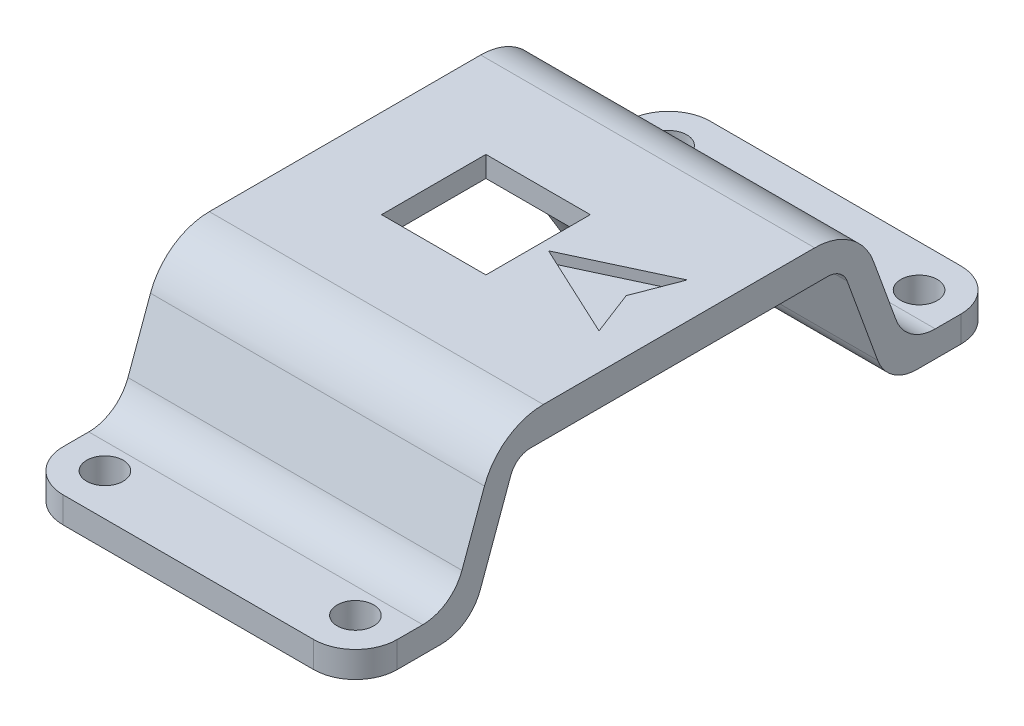
SolidWorks part; units mm, degrees
ref_plane "Спереди" through (0, 0, 0) normal (0, 0, 1) x (1, 0, 0)
ref_plane "Сверху" through (0, 0, 0) normal (0, 1, 0) x (1, 0, 0)
ref_plane "Справа" through (0, 0, 0) normal (1, 0, 0) x (0, 0, -1)
sketch "Эскиз1" plane through (0, 0, 0) normal (1, 0, 0) x (0, 0, -1)
  line L0 (0, 0) -> (0, 19.8413) construction
  line L1 (-31, 0) -> (-20, 0)
  line L2 (-20, 0) -> (-15.6324, 12)
  line L3 (-15.6324, 12) -> (15.6324, 12)
  line L4 (-31, 0) -> (-31, 2.5)
  line L5 (-31, 2.5) -> (-21.7505, 2.5)
  line L6 (-21.7505, 2.5) -> (-17.2009, 15)
  line L7 (-17.2009, 15) -> (17.2009, 15)
  line L8 (21.7505, 2.5) -> (17.2009, 15)
  line L9 (31, 2.5) -> (21.7505, 2.5)
  line L10 (31, 0) -> (31, 2.5)
  line L11 (20, 0) -> (15.6324, 12)
  line L12 (31, 0) -> (20, 0)
  point P14 (0, 15)
  point P18 (0, 12)
  dimension "D1" = 31
  dimension "D2" = 2.5
  dimension "D3" = 3
  dimension "D4" = 2.5
  dimension "D5" = 12
  dimension "D6" = 20
  dimension "D7" = 110
extrude "Бобышка-Вытянуть1" add sketch "Эскиз1" along normal blind 32
sketch "Эскиз2" plane through (0, 0, 0) normal (0, -1, 0) x (1, 0, 0)
  line L0 (0, 0) -> (39.3934, 0) construction
  line L1 (16, 31) -> (16, -31) construction
  line L2 (32, 31) -> (0, 31) construction
  line L3 (32, -31) -> (0, -31) construction
  circle A0 centre (4, 27) radius 1.75
  dimension "D1" = 3.5
  dimension "D2" = 27
  dimension "D3" = 12
extrude "Вырез-Вытянуть1" cut sketch "Эскиз2" against normal through all
pattern_linear "Линейный массив1" count 2 spacing 24 along (1, 0, 0) count 2 spacing 54 along (0, 0, -1) of "Вырез-Вытянуть1"
fillet "Скругление1" radius 4 4 edges at (32, 1.25, -31) (0, 1.25, -31) (0, 1.25, 31) (32, 1.25, 31)
sketch "Эскиз3" plane through (0, 12, 0) normal (0, -1, 0) x (1, 0, 0)
  line L0 (0, 0) -> (32, 0) construction
  line L1 (0, 15.6324) -> (0, -15.6324) construction
  line L2 (32, 15.6324) -> (32, -15.6324) construction
  line L3 (16, 15.6324) -> (16, -15.6324) construction
  line L4 (32, 15.6324) -> (0, 15.6324) construction
  line L5 (32, -15.6324) -> (0, -15.6324) construction
  line L6 (4, 15.6324) -> (4, -15.6324) construction
  line L7 (28, 15.6324) -> (28, -15.6324) construction
  circle A0 centre (26, 10.5) radius 1
  circle A1 centre (26, 10.5) radius 2.5
  dimension "D4" = 2
  dimension "D7" = 5
  dimension "D1" = 32
  dimension "D2" = 4
  dimension "D3" = 4
  dimension "D5" = 2
  dimension "D6" = 10.5
fillet "Скругление3" radius 6 2 edges at (16, 15, -17.2009) (16, 15, 17.2009)
fillet "Скругление5" radius 4 4 edges at (16, 0, -20) (16, 2.5, -21.7505) (16, 0, 20) (16, 2.5, 21.7505)
sketch "Эскиз4" plane through (0, 15, 0) normal (0, 1, 0) x (1, 0, 0)
  line L0 (0, 0) -> (32, 0) construction
  line L1 (32, 12.9996) -> (32, -12.9996) construction
  line L2 (16, 12.9996) -> (16, -12.9996) construction
  line L3 (32, 12.9996) -> (0, 12.9996) construction
  line L4 (0, -12.9996) -> (32, -12.9996) construction
  line L16 (8.5, 5) -> (8.5, -5)
  line L17 (8.5, -5) -> (18.5, -5)
  line L18 (18.5, -5) -> (18.5, 5)
  line L19 (18.5, 5) -> (8.5, 5)
  dimension "D1" = 10
  dimension "D2" = 10
  dimension "D3" = 7.5
  dimension "D4" = 5
extrude "Вырез-Вытянуть3" cut sketch "Эскиз4" against normal through all
fillet "Скругление6" radius 2 2 edges at (16, 12, 15.6324) (16, 12, -15.6324)
extrude "Бобышка-Вытянуть3" add sketch "Эскиз3" along normal blind 3
chamfer "Фаска3" distance 1.75 angle 60 1 edges at (26, 12, 13) first distance on face at (26, 12, 13)
pattern_linear "Линейный массив5" count 2 spacing 12.5 along (-1, 0, 0) count 2 spacing 21 along (0, 0, -1) of "Фаска3", "Бобышка-Вытянуть3"
sketch "Эскиз12" plane through (0, 15, 0) normal (0, 1, 0) x (1, 0, 0)
  line L0 (0, 0) -> (32, 0) construction
  line L1 (32, 12.9996) -> (32, -12.9996) construction
  line L2 (19.5, 0) -> (28.5631, -4.2262)
  line L3 (28.5631, -4.2262) -> (26.9408, 0)
  line L4 (28.5631, 4.2262) -> (26.9408, 0)
  line L5 (19.5, 0) -> (28.5631, 4.2262)
  dimension "D1" = 25
  dimension "D2" = 44
  dimension "D3" = 10
  dimension "D4" = 12.5
extrude "Вырез-Вытянуть5" cut sketch "Эскиз12" against normal blind 1
chamfer "Фаска4" distance 1 angle 45 4 edges at (18.5, 12, 0) (13.5, 12, -5) (13.5, 12, 5) (8.5, 12, 0)
